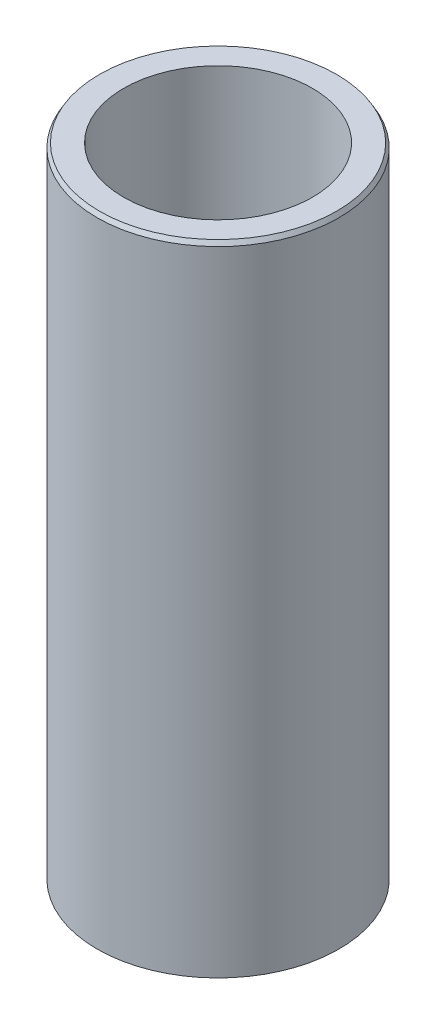
SolidWorks part; units mm, degrees
ref_plane "Front Plane" through (0, 0, 0) normal (0, 0, 1) x (1, 0, 0)
ref_plane "Top Plane" through (0, 0, 0) normal (0, 1, 0) x (1, 0, 0)
ref_plane "Right Plane" through (0, 0, 0) normal (1, 0, 0) x (0, 0, -1)
sketch "Sketch1" plane through (0, 0, 0) normal (0, 1, 0) x (1, 0, 0)
  circle A0 centre (0, 0) radius 30
  dimension "SHAFT_OD" = 60
extrude "Boss-Extrude1" add sketch "Sketch1" along normal blind 158.6773
sketch "Sketch2" plane through (0, 0, 0) normal (0, 1, 0) x (1, 0, 0)
  circle A0 centre (0, 0) radius 23.4029
  dimension "BORE_D" = 46.8057
extrude "Cut-Extrude1" cut sketch "Sketch2" along normal through all
chamfer "Chamfer1" distance 1.0748 angle 30 2 edges at (0, 158.6773, 30) (0, 0, 30) first distance on face at (0, 158.6773, 30) first distance on face at (0, 0, 23.4029)
